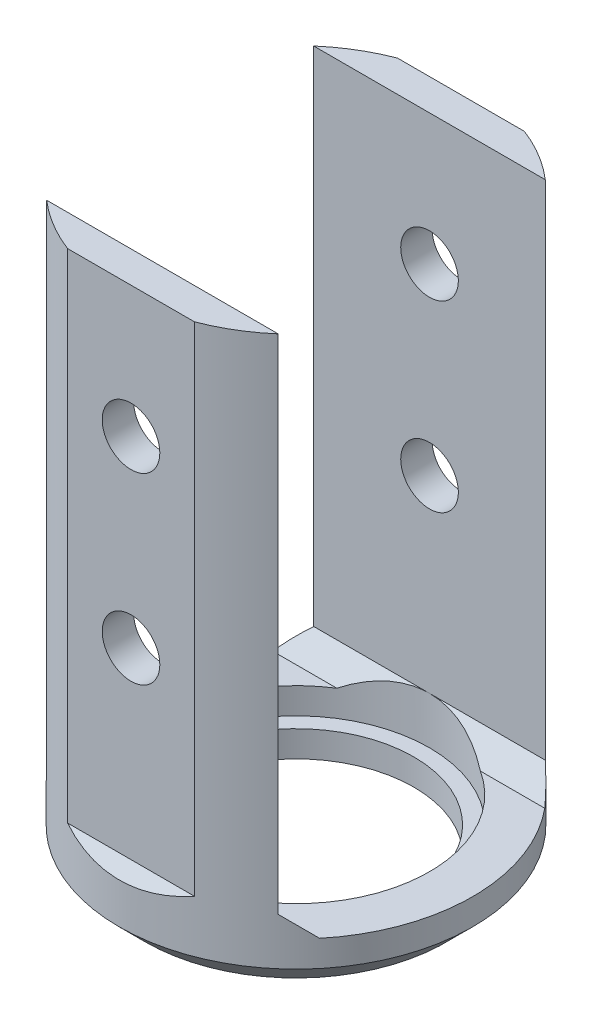
SolidWorks part; units mm, degrees
ref_plane "前视基准面" through (0, 0, 0) normal (0, 0, 1) x (1, 0, 0)
ref_plane "上视基准面" through (0, 0, 0) normal (0, 1, 0) x (1, 0, 0)
ref_plane "右视基准面" through (0, 0, 0) normal (1, 0, 0) x (0, 0, -1)
other "Configuration Table"
sketch "草图1" plane through (0, 0, 0) normal (0, 1, 0) x (1, 0, 0)
  circle A0 centre (0, 0) radius 4.5
  circle A1 centre (0, 0) radius 6.75
  dimension "D1" = 9
  dimension "D2" = 13.5
extrude "凸台-拉伸1" add sketch "草图1" along normal blind 2
sketch "草图2" plane through (0, 2, 0) normal (0, 1, 0) x (1, 0, 0)
  circle A0 centre (0, 0) radius 5.1
  dimension "D1" = 10.2
extrude "切除-拉伸1" cut sketch "草图2" against normal blind 1
sketch "草图3" plane through (0, 2, 0) normal (0, 1, 0) x (1, 0, 0)
  line L0 (-4.4218, 5.1) -> (4.4218, 5.1)
  line L1 (-4.4218, -5.1) -> (4.4218, -5.1)
  line L2 (-2.4233, 6.3) -> (2.4233, 6.3)
  line L3 (-2.4233, -6.3) -> (2.4233, -6.3)
  circle A0 centre (0, 0) radius 6.75
  circle A2 centre (0, 0) radius 6.75 construction
  circle A3 centre (0, 0) radius 5.1 construction
  circle M5 centre (0, 0) radius 6.75
  dimension "D1" = 1.2
  dimension "D2" = 1.2
  dimension "D3" = 10.2
extrude "凸台-拉伸2" add sketch "草图3" along normal blind 20 contours L0 M5 | L1 M5 region at (0, 2, -5.6451) region at (0, 2, 5.6451)
sketch "草图4" plane through (0, 0, 6.3) normal (0, 0, 1) x (1, 0, 0)
  line L0 (-2.4233, 2) -> (2.4233, 2) construction
  circle A0 centre (0, 17) radius 1.1
  circle A1 centre (0, 10) radius 1.1
  dimension "D1" = 2.2
  dimension "D2" = 15
  dimension "D3" = 8
extrude "切除-拉伸2" cut sketch "草图4" against normal blind 20
chamfer "倒角1" distance 1 angle 45 1 edges at (0, 0, 6.75)
chamfer "倒角2" distance 1 angle 45 2 edges at (0, 2, 6.3) (0, 2, -6.3)
sketch "草图5" plane through (0, 22, 0) normal (0, 1, 0) x (1, 0, 0)
  line L0 (-2.4233, -6.3) -> (2.4233, -6.3)
  line L1 (2.4233, -6.3) -> (2.6791, -7.0894)
  line L2 (2.6791, -7.0894) -> (-2.8605, -6.6772)
  line L3 (-2.8605, -6.6772) -> (-2.4233, -6.3)
chamfer "倒角3" distance 0.8 angle 45 4 edges at (2.2109, 2, 5.1) (-2.2109, 2, 5.1) (-2.2109, 2, -5.1) (2.2109, 2, -5.1)
